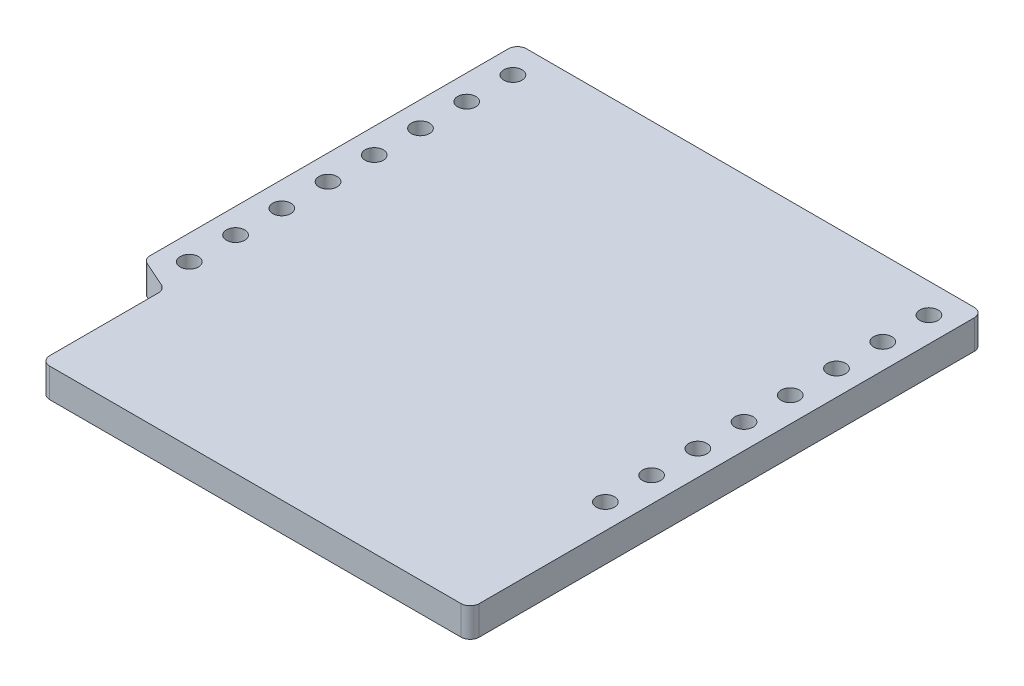
SolidWorks part; units mm, degrees
ref_plane "Front Plane" through (0, 0, 0) normal (0, 0, 1) x (1, 0, 0)
ref_plane "Top Plane" through (0, 0, 0) normal (0, 1, 0) x (1, 0, 0)
ref_plane "Right Plane" through (0, 0, 0) normal (1, 0, 0) x (0, 0, -1)
sketch "Sketch2" plane through (0, 0, 0) normal (0, 1, 0) x (1, 0, 0)
  line L0 (-11.43, 26.58) -> (11.43, 26.58) construction
  line L2 (-12.8, 7.6905) -> (-12.8, 28.2)
  line L3 (-12.8, 28.2) -> (12.8, 28.2)
  line L4 (12.8, 0) -> (12.8, 28.2)
  line L5 (0, 0) -> (0, 28.2) construction
  line L6 (-11.43, 26.58) -> (-11.43, 24.04) construction
  line L7 (-130.1532, 224.7802) -> (936.5135, 224.7802) construction
  line L10 (-12.8, 0) -> (-12.8, 7.6905) construction
  line L11 (-12.8, 0) -> (-10.8, 0) construction
  line L12 (-10.8, 0) -> (12.8, 0)
  line L14 (-10.8, 0) -> (-10.8, 6.8)
  line L15 (-10.8, 6.8) -> (-12.8, 7.6905)
  line L16 (223.547, 458.7027) -> (1290.2137, 458.7027) construction
  circle A0 centre (-11.43, 26.58) radius 0.5
  circle A1 centre (11.43, 26.58) radius 0.5
  circle A2 centre (-11.43, 24.04) radius 0.5
  circle A3 centre (11.43, 24.04) radius 0.5
  circle A4 centre (-11.43, 21.5) radius 0.5
  circle A5 centre (11.43, 21.5) radius 0.5
  circle A6 centre (-11.43, 18.96) radius 0.5
  circle A7 centre (11.43, 18.96) radius 0.5
  circle A8 centre (-11.43, 16.42) radius 0.5
  circle A9 centre (11.43, 16.42) radius 0.5
  circle A10 centre (-11.43, 13.88) radius 0.5
  circle A11 centre (11.43, 13.88) radius 0.5
  circle A12 centre (-11.43, 11.34) radius 0.5
  circle A13 centre (11.43, 11.34) radius 0.5
  circle A14 centre (-11.43, 8.8) radius 0.5
  circle A15 centre (11.43, 8.8) radius 0.5
  point P12 (0, 26.58)
  dimension "D3" = 1
  dimension "D1" = 6.8
  dimension "D2" = 28.2
  dimension "D4" = 22.86
  dimension "D5" = 1.62
  dimension "D7" = 2.54
  dimension "D8" = 25.6
  dimension "D9" = 114
  dimension "D10" = 2
  dimension "D6" = 8
extrude "Boss-Extrude1" add sketch "Sketch2" along normal blind 1.6
fillet "Fillet1" radius 0.5 6 edges at (-10.8, 0.8, 0) (-10.8, 0.8, -6.8) (-12.8, 0.8, -7.6905) (-12.8, 0.8, -28.2) (12.8, 0.8, -28.2) (12.8, 0.8, 0)
ref_axis "Axis1" through (-11.43, 1.6, -26.58) along (0, -1, 0)
ref_axis "Axis2" through (11.43, 1.6, -26.58) along (0, -1, 0)
ref_axis "Axis3" through (-11.43, 1.6, -8.8) along (0, -1, 0)
ref_axis "Axis4" through (11.43, 1.6, -8.8) along (0, -1, 0)
